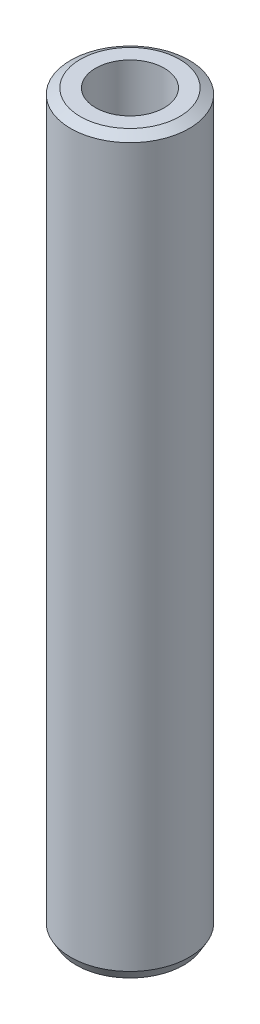
SolidWorks part; units mm, degrees
ref_plane "Front Plane" through (0, 0, 0) normal (0, 0, 1) x (1, 0, 0)
ref_plane "Top Plane" through (0, 0, 0) normal (0, 1, 0) x (1, 0, 0)
ref_plane "Right Plane" through (0, 0, 0) normal (1, 0, 0) x (0, 0, -1)
sketch "Sketch1" plane through (0, 0, 0) normal (0, 1, 0) x (1, 0, 0)
  circle A0 centre (0, 0) radius 40
  dimension "SHAFT_OD" = 80
extrude "Boss-Extrude1" add sketch "Sketch1" along normal blind 494.9483
sketch "Sketch2" plane through (0, 0, 0) normal (0, 1, 0) x (1, 0, 0)
  circle A0 centre (0, 0) radius 23.1864
  dimension "BORE_D" = 46.3729
extrude "Cut-Extrude1" cut sketch "Sketch2" along normal through all
chamfer "Chamfer1" distance 3.7384 angle 60 2 edges at (0, 494.9483, 40) (0, 0, 40) first distance on face at (0, 494.9483, 40) first distance on face at (0, 0, 23.1864)
